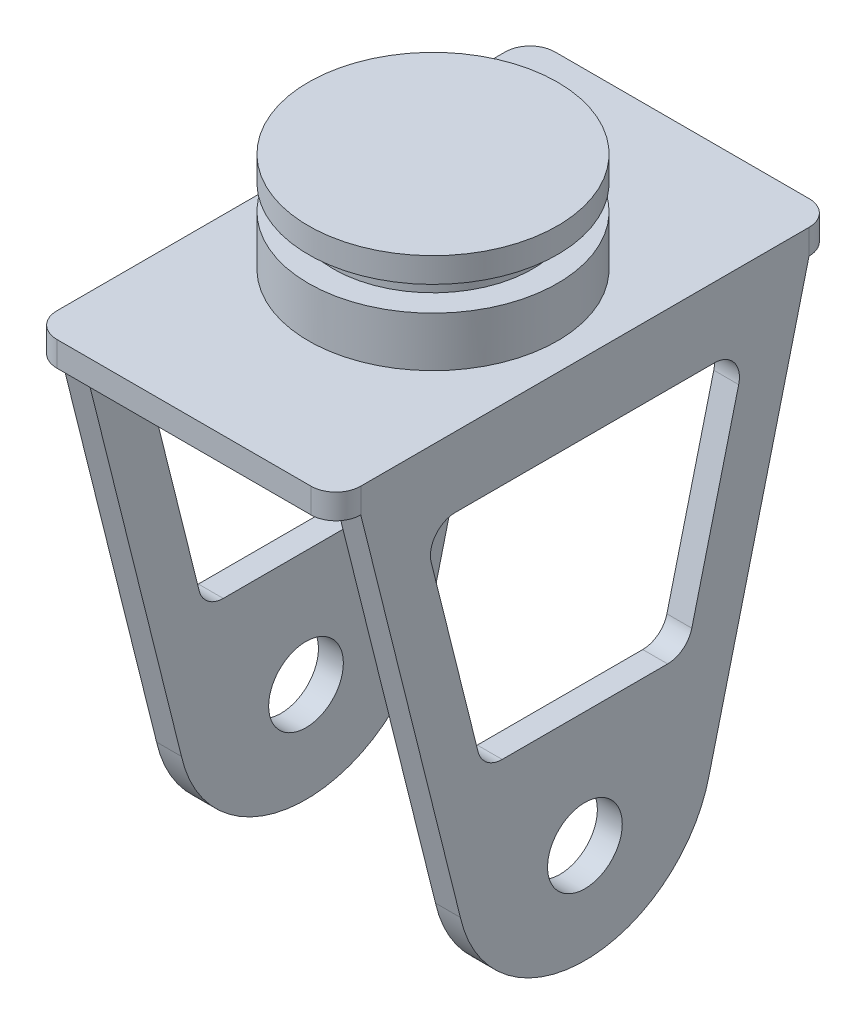
SolidWorks part; units mm, degrees
ref_plane "Front Plane" through (0, 0, 0) normal (0, 0, 1) x (1, 0, 0)
ref_plane "Top Plane" through (0, 0, 0) normal (0, 1, 0) x (1, 0, 0)
ref_plane "Right Plane" through (0, 0, 0) normal (1, 0, 0) x (0, 0, -1)
sketch "Sketch1" plane through (0, 0, 0) normal (0, 1, 0) x (1, 0, 0)
  line L1 (-12.954, -25.4) -> (12.954, -25.4)
  line L2 (-15.494, -22.86) -> (-15.494, 22.86)
  line L3 (-12.954, 25.4) -> (12.954, 25.4)
  line L4 (15.494, -22.86) -> (15.494, 22.86)
  arc A0 (-12.954, -25.4) -> (-15.494, -22.86) centre (-12.954, -22.86) cw
  arc A1 (12.954, -25.4) -> (15.494, -22.86) centre (12.954, -22.86) ccw
  arc A2 (12.954, 25.4) -> (15.494, 22.86) centre (12.954, 22.86) cw
  arc A3 (-15.494, 22.86) -> (-12.954, 25.4) centre (-12.954, 22.86) cw
  dimension "D1" = 2.54
extrude "Boss-Extrude1" add sketch "Sketch1" along normal blind 2.54
sketch "Sketch2" plane through (0, 2.54, 0) normal (0, 1, 0) x (1, 0, 0)
  circle A0 centre (0, 0) radius 12.7
extrude "Boss-Extrude2" add sketch "Sketch2" along normal blind 5.08
sketch "Sketch3" plane through (0, 7.62, 0) normal (0, 1, 0) x (1, 0, 0)
  circle A0 centre (0, 0) radius 10.16
extrude "Boss-Extrude3" add sketch "Sketch3" along normal blind 2.54
sketch "Sketch4" plane through (0, 10.16, 0) normal (0, 1, 0) x (1, 0, 0)
  circle A0 centre (0, 0) radius 12.7
extrude "Boss-Extrude4" add sketch "Sketch4" along normal blind 2.54
sketch "Sketch5" plane through (0, 0, 0) normal (0, -1, 0) x (1, 0, 0)
  line L15 (-12.954, -22.86) -> (-12.954, 22.86)
  line L16 (-12.954, -22.86) -> (-12.954, 22.86)
  line L17 (-12.954, 22.86) -> (-15.494, 22.86)
  line L18 (12.954, 22.86) -> (12.954, -22.86)
  line L19 (12.954, 22.86) -> (12.954, -22.86)
  line L20 (-15.494, 22.86) -> (-15.494, -22.86)
  line L21 (-15.494, -22.86) -> (-12.954, -22.86)
  line L22 (12.954, 22.86) -> (15.494, 22.86)
  line L23 (15.494, 22.86) -> (15.494, -22.86)
  line L24 (15.494, 22.86) -> (15.494, -22.86) construction
  line L25 (15.494, -22.86) -> (12.954, -22.86)
  arc A0 (12.954, -25.4) -> (15.494, -22.86) centre (12.954, -22.86) ccw construction
  dimension "D1" = 2.54
  dimension "D2" = 2.54
extrude "Boss-Extrude5" add sketch "Sketch5" along normal blind 50.8
sketch "Sketch6" plane through (15.494, 0, 0) normal (1, 0, 0) x (0, 0, -1)
  line L0 (-22.86, 0) -> (22.86, 0) construction
  line L2 (22.86, -50.8) -> (-22.86, -50.8) construction
  line L3 (-22.86, 0) -> (-22.86, -50.8)
  line L4 (-22.86, -50.8) -> (22.86, -50.8)
  line L5 (22.86, -50.8) -> (22.86, 0) construction
  line L6 (-22.86, 0) -> (-12.7, -40.64)
  line L7 (22.86, 0) -> (12.7, -40.64)
  line L8 (22.86, -50.8) -> (22.86, 0)
  circle A0 centre (0, -40.64) radius 3.81
  arc A1 (-12.7, -40.64) -> (12.7, -40.64) centre (0, -37.7825) ccw
  line M4 (-22.86, 0) -> (-22.86, -50.8)
  line M5 (-22.86, -50.8) -> (22.86, -50.8)
  line M6 (22.86, -50.8) -> (22.86, 0)
extrude "Cut-Extrude1" cut sketch "Sketch6" against normal blind 2.54 contours A0 region at (15.494, -40.64, 0)
extrude "Cut-Extrude2" cut sketch "Sketch6<3>" against normal blind 30.988 contours A1 L6 M4 M5 | A1 L4 L7 M6 | A0 region at (15.494, -34.7285, 18.0369) region at (15.494, -34.7285, -18.0369) region at (15.494, -40.64, 0)
sketch "Sketch6<3>" plane through (15.494, 0, 0) normal (1, 0, 0) x (0, 0, -1) same geometry as "Sketch6"
sketch "Sketch7" plane through (15.494, 0, 0) normal (1, 0, 0) x (0, 0, -1)
  line L9 (-15.683, -7.7626) -> (-10.9018, -26.8874)
  line L12 (-8.4376, -28.8114) -> (8.4376, -28.8114)
  line L13 (10.9018, -26.8874) -> (15.683, -7.7626)
  line L14 (13.2188, -4.6066) -> (-13.2188, -4.6066)
  arc A0 (-10.9018, -26.8874) -> (-8.4376, -28.8114) centre (-8.4376, -26.2714) ccw
  arc A1 (8.4376, -28.8114) -> (10.9018, -26.8874) centre (8.4376, -26.2714) ccw
  arc A2 (15.683, -7.7626) -> (13.2188, -4.6066) centre (13.2188, -7.1466) ccw
  arc A3 (-15.683, -7.7626) -> (-13.2188, -4.6066) centre (-13.2188, -7.1466) cw
  dimension "D1" = 2.54
extrude "Cut-Extrude3" cut sketch "Sketch7" against normal through all
